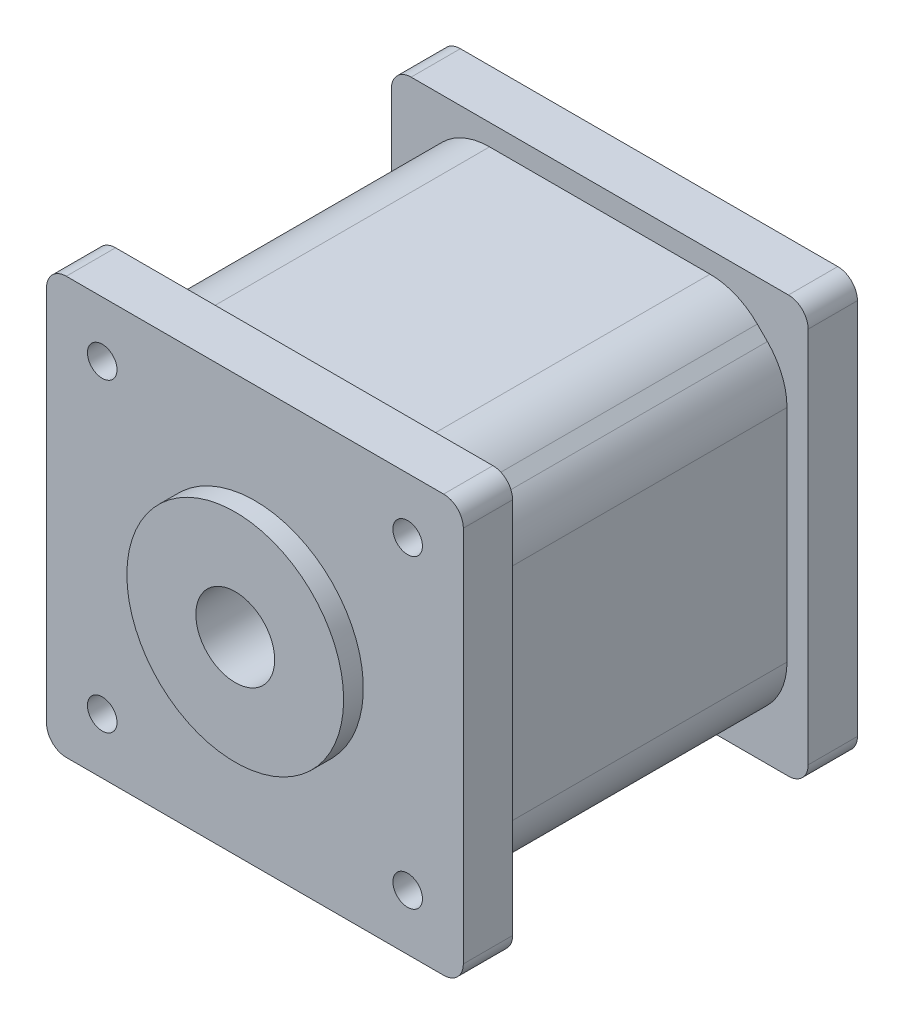
SolidWorks part; units mm, degrees
material "氧化铝"
ref_plane "前视基准面" through (0, 0, 0) normal (0, 0, 1) x (1, 0, 0)
ref_plane "上视基准面" through (0, 0, 0) normal (0, 1, 0) x (1, 0, 0)
ref_plane "右视基准面" through (0, 0, 0) normal (1, 0, 0) x (0, 0, -1)
sketch "草图1" plane through (0, 0, 0) normal (0, 0, 1) x (1, 0, 0)
  line L1 (-19.15, -21.15) -> (19.15, -21.15)
  line L2 (-21.15, -19.15) -> (-21.15, 19.15)
  line L3 (-19.15, 21.15) -> (19.15, 21.15)
  line L4 (21.15, -19.15) -> (21.15, 19.15)
  line L5 (-21.15, -21.15) -> (21.15, 21.15) construction
  line L6 (-21.15, 21.15) -> (21.15, -21.15) construction
  arc A0 (-21.15, 19.15) -> (-19.15, 21.15) centre (-19.15, 19.15) cw
  arc A1 (21.15, -19.15) -> (19.15, -21.15) centre (19.15, -19.15) cw
  arc A2 (19.15, 21.15) -> (21.15, 19.15) centre (19.15, 19.15) cw
  arc A3 (-21.15, -19.15) -> (-19.15, -21.15) centre (-19.15, -19.15) ccw
  point P0 (0, 0)
  dimension "D1" = 2
  dimension "D4" = 2
  dimension "D5" = 2
  dimension "D6" = 2
  dimension "D2" = 42.3
  dimension "D3" = 42.3
extrude "凸台-拉伸1" add sketch "草图1" along normal blind 5 contours L2 A0 L3 A2 L4 A1 L1 A3
sketch "草图2" plane through (0, 0, 5) normal (0, 0, 1) x (1, 0, 0)
  line L0 (-17.0116, 15.9884) -> (-15.9884, 17.0116)
  line L1 (-11.1879, -19) -> (11.1879, -19)
  line L2 (-19, -11.1879) -> (-19, 11.1879)
  line L3 (-11.1879, 19) -> (11.1879, 19)
  line L4 (19, -11.1879) -> (19, 11.1879)
  line L5 (-19, -19) -> (19, 19) construction
  line L6 (-19, 19) -> (19, -19) construction
  line L7 (-15.9884, -17.0116) -> (-17.0116, -15.9884)
  line L8 (15.9884, -17.0116) -> (17.0116, -15.9884)
  line L9 (15.9884, 17.0116) -> (17.0116, 15.9884)
  arc A0 (11.1879, 19) -> (15.9884, 17.0116) centre (11.1879, 12.2111) cw
  arc A1 (17.0116, 15.9884) -> (19, 11.1879) centre (12.2111, 11.1879) cw
  arc A2 (19, -11.1879) -> (17.0116, -15.9884) centre (12.2111, -11.1879) cw
  arc A3 (15.9884, -17.0116) -> (11.1879, -19) centre (11.1879, -12.2111) cw
  arc A4 (-11.1879, -19) -> (-15.9884, -17.0116) centre (-11.1879, -12.2111) cw
  arc A5 (-17.0116, -15.9884) -> (-19, -11.1879) centre (-12.2111, -11.1879) cw
  arc A6 (-17.0116, 15.9884) -> (-19, 11.1879) centre (-12.2111, 11.1879) ccw
  arc A7 (-11.1879, 19) -> (-15.9884, 17.0116) centre (-11.1879, 12.2111) ccw
  point P0 (0, 0)
  point P16 (14, 19)
  point P19 (19, 14)
  point P22 (19, -14)
  point P25 (14, -19)
  point P28 (-14, -19)
  point P31 (-19, -14)
  point P34 (-19, 14)
  point P37 (-14, 19)
  dimension "D3" = 6.7889
  dimension "D1" = 38
  dimension "D2" = 38
extrude "凸台-拉伸2" add sketch "草图2" along normal blind 30
sketch "草图3" plane through (0, 0, 35) normal (0, 0, 1) x (1, 0, 0)
  line L1 (-19.15, -21.15) -> (19.15, -21.15)
  line L2 (-21.15, -19.15) -> (-21.15, 19.15)
  line L3 (-19.15, 21.15) -> (19.15, 21.15)
  line L4 (21.15, -19.15) -> (21.15, 19.15)
  line L5 (-21.15, -21.15) -> (21.15, 21.15) construction
  line L6 (-21.15, 21.15) -> (21.15, -21.15) construction
  arc A0 (19.15, 21.15) -> (21.15, 19.15) centre (19.15, 19.15) cw
  arc A1 (21.15, -19.15) -> (19.15, -21.15) centre (19.15, -19.15) cw
  arc A2 (-19.15, -21.15) -> (-21.15, -19.15) centre (-19.15, -19.15) cw
  arc A3 (-19.15, 21.15) -> (-21.15, 19.15) centre (-19.15, 19.15) ccw
  point P0 (0, 0)
  dimension "D3" = 2
  dimension "D1" = 42.3
  dimension "D2" = 42.3
extrude "凸台-拉伸4" add sketch "草图3" along normal blind 5
sketch "草图4" plane through (0, 0, 40) normal (0, 0, 1) x (1, 0, 0)
  circle A0 centre (15.5, 15.5) radius 1.5
  circle A1 centre (15.5, -15.5) radius 1.5
  circle A2 centre (-15.5, -15.5) radius 1.5
  circle A3 centre (-15.5, 15.5) radius 1.5
  dimension "D1" = 4
extrude "切除-拉伸1" cut sketch "草图4" against normal blind 4.5
sketch "草图5" plane through (0, 0, 40) normal (0, 0, 1) x (1, 0, 0)
  circle A0 centre (0, 0) radius 11
extrude "凸台-拉伸5" add sketch "草图5" along normal blind 2
sketch "草图6" plane through (0, 0, 42) normal (0, 0, 1) x (1, 0, 0)
  circle A0 centre (0, 0) radius 4
extrude "切除-拉伸2" cut sketch "草图6" against normal blind 20
